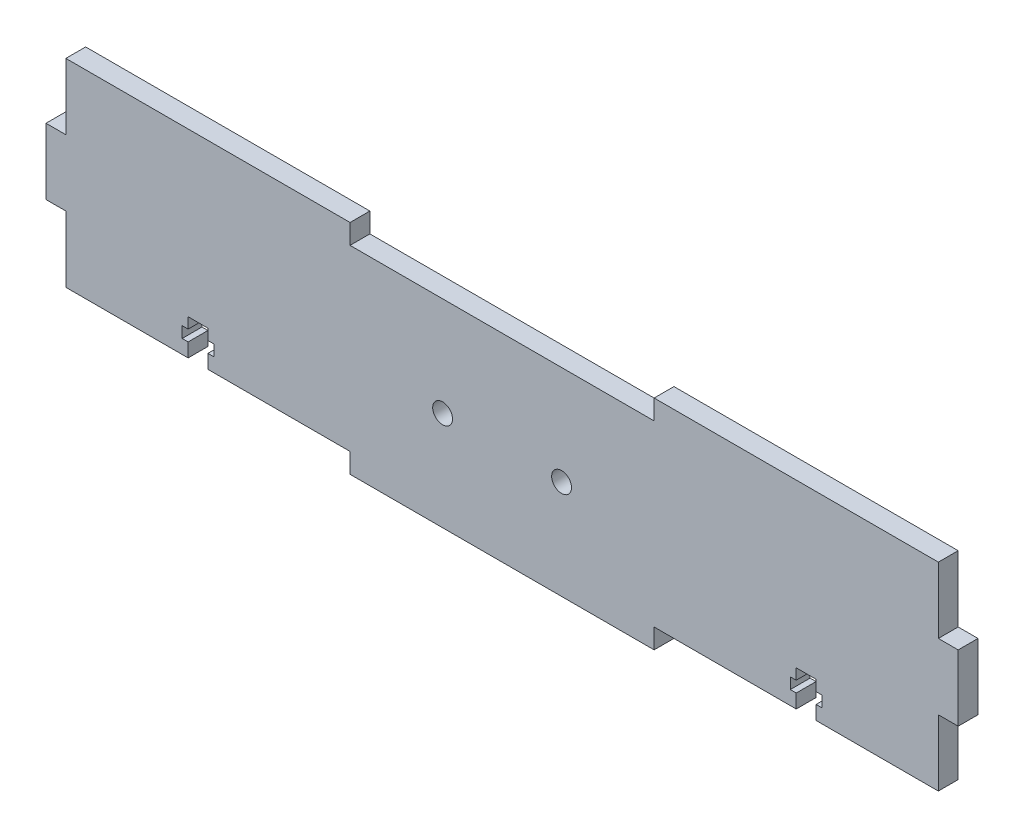
SolidWorks part; units mm, degrees
ref_plane "Alzado" through (0, 0, 0) normal (0, 0, 1) x (1, 0, 0)
ref_plane "Planta" through (0, 0, 0) normal (0, 1, 0) x (1, 0, 0)
ref_plane "Vista lateral" through (0, 0, 0) normal (1, 0, 0) x (0, 0, -1)
sketch "Croquis1" plane through (0, 0, 0) normal (0, 0, 1) x (1, 0, 0)
  line L0 (115, 0) -> (115, 23.3303) construction
  line L1 (0, 0) -> (230, 0)
  line L2 (0, 0) -> (0, 55)
  line L3 (0, 55) -> (230, 55)
  line L4 (230, 0) -> (230, 55)
  line L5 (0, 55) -> (5, 55)
  line L6 (0, 55) -> (0, 0)
  line L7 (0, 0) -> (5, 0)
  line L8 (5, 55) -> (5, 0)
  line L9 (225, 55) -> (225, 0)
  line L10 (76.6667, 5) -> (76.6667, 0)
  line L11 (0, 0) -> (230, 0)
  line L12 (0, 0) -> (0, 5)
  line L13 (0, 5) -> (230, 5)
  line L14 (230, 0) -> (230, 5)
  line L15 (153.3333, 0) -> (153.3333, 5)
  line L16 (0, 38.3333) -> (5, 38.3333)
  line L17 (5, 21.6667) -> (0, 21.6667)
  line L18 (225, 21.6667) -> (230, 21.6667)
  line L19 (230, 38.3333) -> (225, 38.3333)
  point P21 (2.5, 38.3333)
  dimension "D1" = 230
  dimension "D2" = 55
  dimension "D3" = 5
  dimension "D4" = 5
  dimension "D5" = 76.6667
  dimension "D6" = 76.6667
  dimension "D7" = 16.6667
  dimension "D8" = 16.6667
extrude "Saliente-Extruir1" add sketch "Croquis1" along normal blind 5 contours L17 L8 L16 L2 | L4 L19 L9 L18 | L0 L11 L15 L13 | L1 L0 L13 L10 | L8 L13 L9 L3 region at (95.8333, 2.5, 0) region at (134.1667, 2.5, 0) region at (115, 30, 0) region at (2.5, 30, 0) region at (227.5, 30, 0)
sketch "Croquis2" plane through (0, 0, 5) normal (0, 0, 1) x (1, 0, 0)
  line L0 (38.3333, 5) -> (38.3333, 14) construction
  line L1 (5, 5) -> (76.6667, 5) construction
  line L2 (115, 0) -> (115, 11.3726) construction
  line L3 (76.6667, 0) -> (153.3333, 0) construction
  line L4 (35.8333, 5) -> (35.8333, 8.5)
  line L5 (35.8333, 8.5) -> (34.3333, 8.5)
  line L6 (34.3333, 8.5) -> (34.3333, 11.3)
  line L7 (34.3333, 11.3) -> (35.8333, 11.3)
  line L8 (35.8333, 11.3) -> (35.8333, 14)
  line L9 (35.8333, 14) -> (40.8333, 14)
  line L10 (40.8333, 11.3) -> (40.8333, 14)
  line L11 (42.3333, 11.3) -> (40.8333, 11.3)
  line L12 (42.3333, 8.5) -> (42.3333, 11.3)
  line L13 (40.8333, 8.5) -> (42.3333, 8.5)
  line L14 (40.8333, 5) -> (40.8333, 8.5)
  line L15 (191.6667, 5) -> (191.6667, 14) construction
  line L16 (189.1667, 5) -> (189.1667, 8.5)
  line L17 (189.1667, 8.5) -> (187.6667, 8.5)
  line L18 (187.6667, 8.5) -> (187.6667, 11.3)
  line L19 (187.6667, 11.3) -> (189.1667, 11.3)
  line L20 (189.1667, 11.3) -> (189.1667, 14)
  line L21 (194.1667, 14) -> (189.1667, 14)
  line L22 (194.1667, 11.3) -> (194.1667, 14)
  line L23 (195.6667, 11.3) -> (194.1667, 11.3)
  line L24 (195.6667, 8.5) -> (195.6667, 11.3)
  line L25 (194.1667, 8.5) -> (195.6667, 8.5)
  line L26 (194.1667, 5) -> (194.1667, 8.5)
  line L27 (40.8333, 5) -> (35.8333, 5)
  line L28 (194.1667, 5) -> (189.1667, 5)
  line L29 (0, 21.6667) -> (0, 38.3333) construction
  point P10 (35.0833, 11.3)
  point P38 (38.3333, 9.5)
  dimension "D1" = 2.8
  dimension "D2" = 4
  dimension "D3" = 9
  dimension "D4" = 3.5
  dimension "D5" = 2.5
  dimension "D6" = 38.3333
extrude "Cortar-Extruir1" cut sketch "Croquis2" against normal blind 5
sketch "Croquis3" plane through (0, 0, 5) normal (0, 0, 1) x (1, 0, 0)
  line L0 (5, 55) -> (225, 55) construction
  line L1 (76.6667, 55) -> (153.3333, 55)
  line L2 (76.6667, 55) -> (76.6667, 50)
  line L3 (76.6667, 50) -> (153.3333, 50)
  line L4 (153.3333, 55) -> (153.3333, 50)
  line L5 (0, 21.6667) -> (0, 38.3333) construction
  line L6 (230, 21.6667) -> (230, 38.3333) construction
  dimension "D1" = 5
  dimension "D2" = 76.6667
  dimension "D3" = 76.6667
extrude "Cortar-Extruir2" cut sketch "Croquis3" against normal blind 10
sketch "Croquis4" plane through (0, 0, 5) normal (0, 0, 1) x (1, 0, 0)
  line L0 (115, 0) -> (115, 25) construction
  line L1 (76.6667, 0) -> (153.3333, 0) construction
  line L2 (100, 25) -> (115, 25) construction
  line L3 (40.8333, 5) -> (76.6667, 5) construction
  circle A0 centre (100, 25) radius 2.5
  circle A1 centre (130, 25) radius 2.5
  dimension "D1" = 5
  dimension "D2" = 15
  dimension "D3" = 20
extrude "Cortar-Extruir3" cut sketch "Croquis4" against normal blind 10
sketch "Croquis5" plane through (0, 0, 5) normal (0, 0, 1) x (1, 0, 0)
  line L44 (76.6667, 50) -> (76.6667, 55)
  line L45 (76.6667, 55) -> (5, 55)
  line L46 (5, 55) -> (5, 38.3333)
  line L47 (5, 38.3333) -> (0, 38.3333)
  line L48 (0, 38.3333) -> (0, 21.6667)
  line L49 (0, 21.6667) -> (5, 21.6667)
  line L50 (5, 21.6667) -> (5, 5)
  line L51 (5, 5) -> (35.8333, 5)
  line L52 (35.8333, 5) -> (35.8333, 8.5)
  line L53 (35.8333, 8.5) -> (34.3333, 8.5)
  line L54 (34.3333, 8.5) -> (34.3333, 11.3)
  line L55 (34.3333, 11.3) -> (35.8333, 11.3)
  line L56 (35.8333, 11.3) -> (35.8333, 14)
  line L57 (35.8333, 14) -> (40.8333, 14)
  line L58 (40.8333, 14) -> (40.8333, 11.3)
  line L59 (40.8333, 11.3) -> (42.3333, 11.3)
  line L60 (42.3333, 11.3) -> (42.3333, 8.5)
  line L61 (42.3333, 8.5) -> (40.8333, 8.5)
  line L62 (40.8333, 8.5) -> (40.8333, 5)
  line L63 (40.8333, 5) -> (76.6667, 5)
  line L64 (76.6667, 5) -> (76.6667, 0)
  line L65 (76.6667, 0) -> (153.3333, 0)
  line L66 (153.3333, 0) -> (153.3333, 5)
  line L67 (153.3333, 5) -> (189.1667, 5)
  line L68 (189.1667, 5) -> (189.1667, 8.5)
  line L69 (189.1667, 8.5) -> (187.6667, 8.5)
  line L70 (187.6667, 8.5) -> (187.6667, 11.3)
  line L71 (187.6667, 11.3) -> (189.1667, 11.3)
  line L72 (189.1667, 11.3) -> (189.1667, 14)
  line L73 (189.1667, 14) -> (194.1667, 14)
  line L74 (194.1667, 14) -> (194.1667, 11.3)
  line L75 (194.1667, 11.3) -> (195.6667, 11.3)
  line L76 (195.6667, 11.3) -> (195.6667, 8.5)
  line L77 (195.6667, 8.5) -> (194.1667, 8.5)
  line L78 (194.1667, 8.5) -> (194.1667, 5)
  line L79 (194.1667, 5) -> (225, 5)
  line L80 (225, 5) -> (225, 21.6667)
  line L81 (225, 21.6667) -> (230, 21.6667)
  line L82 (230, 21.6667) -> (230, 38.3333)
  line L83 (230, 38.3333) -> (225, 38.3333)
  line L84 (225, 38.3333) -> (225, 55)
  line L85 (225, 55) -> (153.3333, 55)
  line L86 (153.3333, 55) -> (153.3333, 50)
  line L87 (153.3333, 50) -> (76.6667, 50)
  line L88 (76.6667, 50) -> (76.6667, 55)
  line L89 (76.6667, 55) -> (5, 55)
  line L90 (5, 55) -> (5, 38.3333)
  line L91 (5, 38.3333) -> (0, 38.3333)
  line L92 (0, 38.3333) -> (0, 21.6667)
  line L93 (0, 21.6667) -> (5, 21.6667)
  line L94 (5, 21.6667) -> (5, 5)
  line L95 (5, 5) -> (35.8333, 5)
  line L96 (35.8333, 5) -> (35.8333, 8.5)
  line L97 (35.8333, 8.5) -> (34.3333, 8.5)
  line L98 (34.3333, 8.5) -> (34.3333, 11.3)
  line L99 (34.3333, 11.3) -> (35.8333, 11.3)
  line L100 (35.8333, 11.3) -> (35.8333, 14)
  line L101 (35.8333, 14) -> (40.8333, 14)
  line L102 (40.8333, 14) -> (40.8333, 11.3)
  line L103 (40.8333, 11.3) -> (42.3333, 11.3)
  line L104 (42.3333, 11.3) -> (42.3333, 8.5)
  line L105 (42.3333, 8.5) -> (40.8333, 8.5)
  line L106 (40.8333, 8.5) -> (40.8333, 5)
  line L107 (40.8333, 5) -> (76.6667, 5)
  line L108 (76.6667, 5) -> (76.6667, 0)
  line L109 (76.6667, 0) -> (153.3333, 0)
  line L110 (153.3333, 0) -> (153.3333, 5)
  line L111 (153.3333, 5) -> (189.1667, 5)
  line L112 (189.1667, 5) -> (189.1667, 8.5)
  line L113 (189.1667, 8.5) -> (187.6667, 8.5)
  line L114 (187.6667, 8.5) -> (187.6667, 11.3)
  line L115 (187.6667, 11.3) -> (189.1667, 11.3)
  line L116 (189.1667, 11.3) -> (189.1667, 14)
  line L117 (189.1667, 14) -> (194.1667, 14)
  line L118 (194.1667, 14) -> (194.1667, 11.3)
  line L119 (194.1667, 11.3) -> (195.6667, 11.3)
  line L120 (195.6667, 11.3) -> (195.6667, 8.5)
  line L121 (195.6667, 8.5) -> (194.1667, 8.5)
  line L122 (194.1667, 8.5) -> (194.1667, 5)
  line L123 (194.1667, 5) -> (225, 5)
  line L124 (225, 5) -> (225, 21.6667)
  line L125 (225, 21.6667) -> (230, 21.6667)
  line L126 (230, 21.6667) -> (230, 38.3333)
  line L127 (230, 38.3333) -> (225, 38.3333)
  line L128 (225, 38.3333) -> (225, 55)
  line L129 (225, 55) -> (153.3333, 55)
  line L130 (153.3333, 55) -> (153.3333, 50)
  line L131 (153.3333, 50) -> (76.6667, 50)
  circle A0 centre (130, 25) radius 2.5 construction
  circle A1 centre (100, 25) radius 2.5 construction
  circle A2 centre (130, 25) radius 2.5
  circle A3 centre (100, 25) radius 2.5
  dimension "D1" = 0
